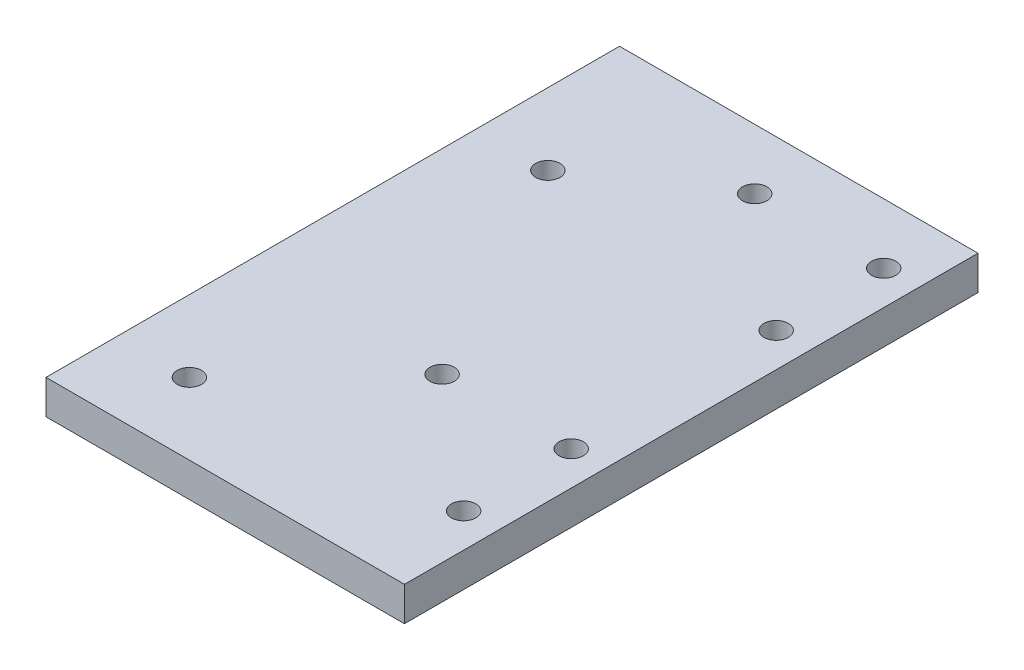
SolidWorks part; units mm, degrees
material "6061 Alloy"
ref_plane "Front Plane" through (0, 0, 0) normal (0, 0, 1) x (1, 0, 0)
ref_plane "Top Plane" through (0, 0, 0) normal (0, 1, 0) x (1, 0, 0)
ref_plane "Right Plane" through (0, 0, 0) normal (1, 0, 0) x (0, 0, -1)
sketch "Sketch1" plane through (0, 0, 0) normal (0, 1, 0) x (1, 0, 0)
  line L0 (0, 0) -> (0, 90)
  line L1 (0, 90) -> (50, 90)
  line L2 (50, 90) -> (50, 10)
  line L3 (50, 10) -> (20, 10)
  line L4 (20, 10) -> (20, 0)
  line L5 (0, 0) -> (20, 0)
  line L12 (20, 10) -> (0, 10)
  line L16 (20, 3.65) -> (20, 10) construction
  line L17 (14.5, 3.175) -> (5.5, 3.175) construction
  circle A5 centre (45.25, 81.6) radius 1.7
  circle A6 centre (14.5, 3.175) radius 1.55
  circle A7 centre (27.25, 81.6) radius 1.7
  circle A9 centre (5.5, 3.175) radius 1.55
  circle A15 centre (45.25, 23) radius 1.7
  circle A16 centre (45.25, 38) radius 1.7
  circle A17 centre (27.25, 38) radius 1.7
  circle A18 centre (45.25, 66.6) radius 1.7
  circle A19 centre (10, 20) radius 1.7
  circle A20 centre (10, 70) radius 1.7
  point P20 (10, 3.175)
  point P21 (10, 0)
  point P36 (10, 10)
  dimension "D2" = 3.1
  dimension "D3" = 3.1
  dimension "D13" = 3.4
  dimension "D1" = 80
  dimension "D9" = 50
  dimension "D11" = 10
  dimension "D4" = 9
  dimension "D5" = 3.175
  dimension "D6" = 15
  dimension "D7" = 8.4
  dimension "D8" = 10
  dimension "D10" = 50
  dimension "D12" = 27.25
  dimension "D14" = 18
  dimension "D15" = 15
  dimension "D16" = 13
extrude "Boss-Extrude1" add sketch "Sketch1" along normal blind 4.7625 contours L12 L3 L2 L1 L0 A20 A19 A18 A17 A16 A15 A7 A5 region at (24.8717, 0, -49.9565)
equation "\"D3@Sketch1\"=\"D2@Sketch1\""
